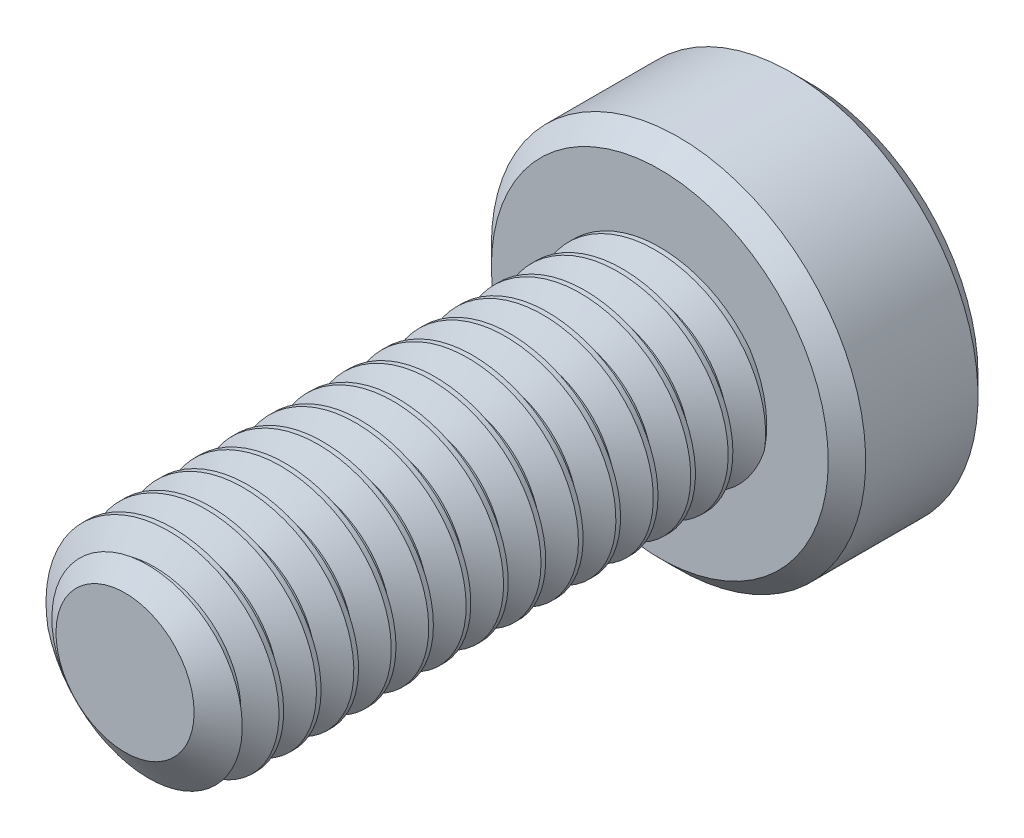
SolidWorks part; units mm, degrees
other "DetailItem1"
ref_plane "Front Plane" through (0, 0, 0) normal (0, 0, 1) x (1, 0, 0)
ref_plane "Top Plane" through (0, 0, 0) normal (0, 1, 0) x (1, 0, 0)
ref_plane "Right Plane" through (0, 0, 0) normal (1, 0, 0) x (0, 0, -1)
sketch "Sketch1" plane through (0, 0, 0) normal (0, 0, 1) x (1, 0, 0)
  circle A0 centre (0, 0) radius 2
  dimension "OD" = 4
extrude "Extrude1" add sketch "Sketch1" against normal blind 10
sketch "Sketch2" plane through (0, 0, 0) normal (0, 0, 1) x (1, 0, 0)
  circle A0 centre (0, 0) radius 2 construction
  circle A1 centre (0, 0) radius 2
curve "Helix/Spiral1" pitch 0.7 height 10.7 radius 2 centre (0, 0, 0) axis (0, 0, -1) start towards (0, 1, 0) parameters "pitch"=0.7
sketch "Sketch3" plane through (0, 0, 0) normal (1, 0, 0) x (0, 0, -1)
  line L0 (-0.6125, 2) -> (-0.35, 1.5453)
  line L1 (-0.35, 1.5453) -> (-0.2625, 1.5453)
  line L2 (-0.2625, 1.5453) -> (0, 2)
  line L3 (-0.6125, 2) -> (0, 2)
  line L4 (-0.3062, 2) -> (-0.3062, 1.5453) construction
  line L5 (-0.4813, 1.7727) -> (-0.1313, 1.7727) construction
  line L6 (0, 2) -> (0, -2) construction
  dimension "D1" = 0.0875
  dimension "D2" = 0.35
  dimension "D3" = 60
sweep "Cut-Sweep1" cut profiles "Sketch3" path "Helix/Spiral1" align with end faces yes
sketch "Sketch4" plane through (0, 0, 0) normal (1, 0, 0) x (0, 0, -1)
  line L0 (0.4962, 2) -> (0, 1.2913)
  line L1 (0, 1.2913) -> (0, 2)
  line L2 (0.4962, 2) -> (0, 2)
  line L3 (-0.6125, 2) -> (0, 2) construction
  line L4 (0, 0) -> (7.0209, 0) construction
  dimension "D1" = 55
  dimension "D2" = 0.254
revolve "Cut-Revolve1" cut sketch "Sketch4" angle 360 about L4
sketch "Sketch6" plane through (0, 0, -10) normal (0, 0, -1) x (-1, 0, 0)
  circle A0 centre (0, 0) radius 3.5
  dimension "head dia" = 7
extrude "Extrude2" add sketch "Sketch6" along normal blind 2.8
sketch "Sketch7" plane through (0, 0, -12.8) normal (0, 0, -1) x (-1, 0, 0)
  line L1 (0, 1.4434) -> (-1.25, 0.7217)
  line L2 (-1.25, 0.7217) -> (-1.25, -0.7217)
  line L3 (-1.25, -0.7217) -> (0, -1.4434)
  line L4 (0, -1.4434) -> (1.25, -0.7217)
  line L5 (1.25, -0.7217) -> (1.25, 0.7217)
  line L6 (1.25, 0.7217) -> (0, 1.4434)
  circle A0 centre (0, 0) radius 1.25 construction
  dimension "hex dia" = 2.5
extrude "Cut-Extrude1" cut sketch "Sketch7" against normal blind 1.875
sketch "Sketch8" plane through (0, 0, -12.8) normal (0, 0, -1) x (-1, 0, 0)
  circle A0 centre (0, 0) radius 1.4434
extrude "Cut-Extrude2" cut sketch "Sketch8" against normal through all draft 45
chamfer "Chamfer1" distance 0.35 angle 45 2 edges at (-3.5, 0, -12.8) (-3.5, 0, -10)
sketch "Sketch10" plane through (0, 0, -10) normal (0, 0, 1) x (1, 0, 0)
  circle A1 centre (0, 0) radius 2
  circle A2 centre (0, 0) radius 2
  dimension "D1" = 0
ref_plane "Plane1" through (0, 0, -12) normal (0, 0, 1) x (1, 0, 0)
extrude "partial thread" [suppressed] add sketch "Sketch10" along normal up to surface (8 mm away) separate body up to plane "Plane1"
chamfer "Chamfer2" [suppressed] distance 0.08 angle 45
combine bodies "Combine1" [suppressed] operation type add bodies to combine 107 108
sketch "Sketch9" plane through (0, 0, 0) normal (1, 0, 0) x (0, 0, -1)
  line L0 (0, 2) -> (0, -2) construction
  line L1 (1.75, 2) -> (1.75, -2) construction
  dimension "D1" = 1.75
equation "\"D3@Helix/Spiral1\" = \"screw length@Extrude1\"+\"pitch@Helix/Spiral1\""
equation "\"D1@Sketch3\" = \"pitch@Helix/Spiral1\"*.125"
equation "\"D2@Sketch3\" = \"pitch@Helix/Spiral1\"*.5"
equation "\"D1@Cut-Extrude1\" = \"hex dia@Sketch7\"*.75"
equation "\"D1@Chamfer1\" = \"head dia@Sketch6\"*.05"
equation "\"D1@Sketch9\" = \"pitch@Helix/Spiral1\"*2.5"
equation "\"D1@Chamfer2\"=\"OD@Sketch1\"*.02"
